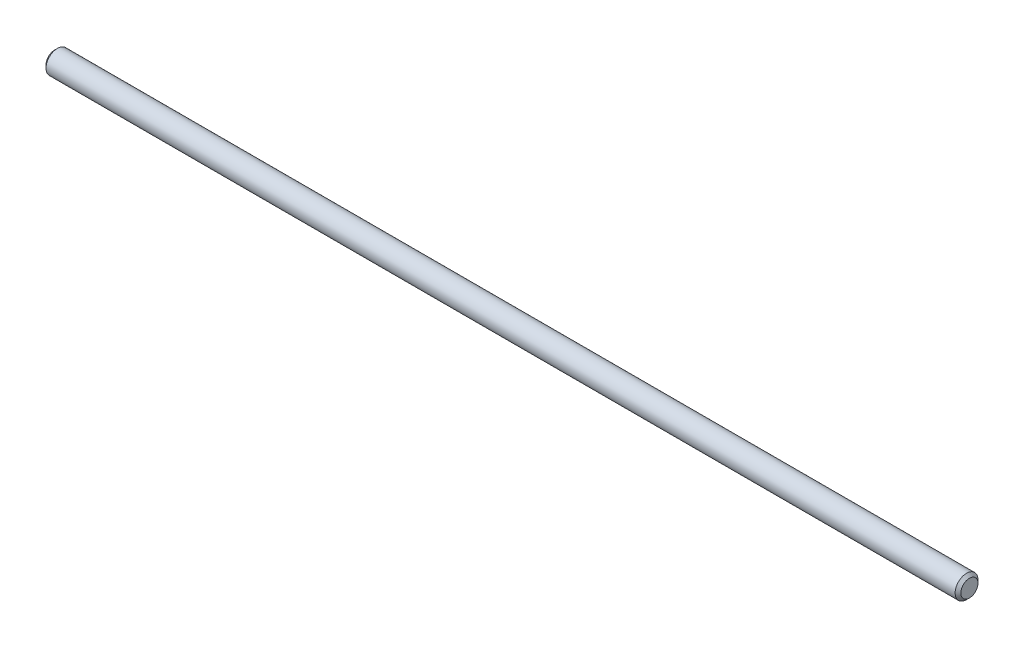
SolidWorks part; units mm, degrees
ref_plane "Front Plane" through (0, 0, 0) normal (0, 0, 1) x (1, 0, 0)
ref_plane "Top Plane" through (0, 0, 0) normal (0, 1, 0) x (1, 0, 0)
ref_plane "Right Plane" through (0, 0, 0) normal (1, 0, 0) x (0, 0, -1)
sketch "Sketch1" plane through (0, 0, 0) normal (0, 0, 1) x (1, 0, 0)
  line L0 (-37.5, 0) -> (37.5, 0) construction
  line L1 (37.5, 1.5) -> (37.5, -1.5) construction
  line L2 (-37.5, 1.5) -> (-37.5, -1.5) construction
  point P6 (35.75, -1.5)
  dimension "Thread Diameter" = 3
  dimension "Length" = 75
  dimension "D1" = 1.75
sketch "Sketch2" plane through (0, 0, 0) normal (1, 0, 0) x (0, 0, -1)
  circle A0 centre (0, 0) radius 1.5
extrude "Boss-Extrude1" add sketch "Sketch2" against normal mid plane 120
sketch "Sketch3" plane through (60, 0, 0) normal (1, 0, 0) x (0, 0, -1)
  circle A1 centre (0, 0) radius 1.5
  circle A2 centre (0, 0) radius 1.5
  dimension "D1" = 0
curve "Helix/Spiral1" pitch 0.5 height 75.5 turns 151 parameters "Pitch"=0.5
chamfer "Chamfer1" distance 0.375 angle 45 2 edges at (-60, 0, -1.5) (60, 0, -1.5)
sketch "Sketch4" plane through (0, 0, 0) normal (0, 0, 1) x (1, 0, 0)
  line L0 (37.4688, 1.5541) -> (37.7188, 1.1211) construction
  line L1 (37.7188, 1.1211) -> (37.9688, 1.5541) construction
  line L2 (37.9688, 1.5541) -> (37.4688, 1.5541) construction
  line L3 (37.7188, 1.5541) -> (37.7188, 1.5) construction
  line L4 (37.7188, 1.1211) -> (37.7188, 1.1752) construction
  line L5 (37.6875, 1.1752) -> (37.75, 1.1752) construction
  line L6 (37.5, 1.5) -> (37.9375, 1.5) construction
  line L7 (37.6875, 1.1752) -> (37.4844, 1.5271)
  line L8 (37.6875, 1.1752) -> (37.75, 1.1752)
  line L9 (37.4844, 1.5271) -> (37.9531, 1.5271)
  line L10 (37.9531, 1.5271) -> (37.75, 1.1752)
  point P13 (37.7188, 1.5271)
  dimension "D2" = 0.0625
sweep "Cut-Sweep3" [suppressed] cut profiles "Sketch4" path "Helix/Spiral1"
equation "\"D3@Helix/Spiral1\" = \"Length@Sketch1\"+\"Pitch@Helix/Spiral1\""
equation "\"D1@Chamfer1\" = \"Pitch@Helix/Spiral1\"*.75"
equation "\"D1@Sketch4\" = \"Pitch@Helix/Spiral1\""
equation "\"D2@Sketch4\" = \"D1@Sketch4\"/8"
equation "\"D1@Sketch1\" = \"Pitch@Helix/Spiral1\"*3.50"
